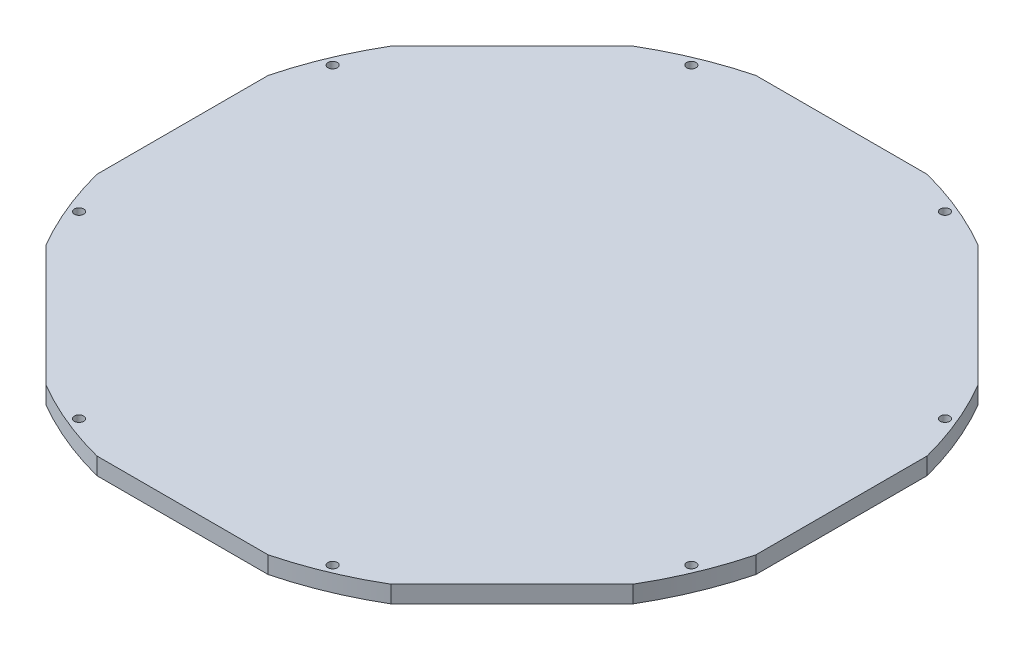
SolidWorks part; units mm, degrees
ref_plane "Front Plane" through (0, 0, 0) normal (0, 0, 1) x (1, 0, 0)
ref_plane "Top Plane" through (0, 0, 0) normal (0, 1, 0) x (1, 0, 0)
ref_plane "Right Plane" through (0, 0, 0) normal (1, 0, 0) x (0, 0, -1)
sketch "Sketch1" plane through (0, 0, 0) normal (0, 1, 0) x (1, 0, 0)
  line L1 (-50.6583, 122.3) -> (-122.3, 50.6583)
  line L2 (-122.3, 50.6583) -> (-122.3, -50.6583)
  line L3 (-122.3, -50.6583) -> (-50.6583, -122.3)
  line L4 (-50.6583, -122.3) -> (50.6583, -122.3)
  line L5 (50.6583, -122.3) -> (122.3, -50.6583)
  line L6 (122.3, -50.6583) -> (122.3, 50.6583)
  line L7 (122.3, 50.6583) -> (50.6583, 122.3)
  line L8 (50.6583, 122.3) -> (-50.6583, 122.3)
  circle A0 centre (0, 0) radius 122.3 construction
  circle A1 centre (0, 0) radius 126.365
  dimension "D2" = 252.73
  dimension "D1" = 244.6
extrude "Boss-Extrude1" add sketch "Sketch1" along normal blind 6.35 contours L4 A1 L5 L6 L7 L8 L1 L2 L3 region at (0, 0, 0)
sketch "Sketch2" plane through (0, 0, 0) normal (0, -1, 0) x (1, 0, 0)
  circle A0 centre (0, 0) radius 115.2525
  circle A1 centre (0, 0) radius 119.0625
  dimension "D1" = 238.125
  dimension "D2" = 230.505
extrude "Cut-Extrude1" cut sketch "Sketch2" against normal blind 2.667
sketch "Sketch3" plane through (0, 6.35, 0) normal (0, 1, 0) x (1, 0, 0)
  line L0 (-63.9978, 108.9605) -> (-31.7934, 122.3) construction
  line L2 (-43.181, 104.2481) -> (-51.6782, 124.7623) construction
  circle A0 centre (0, 0) radius 122.9995
  point P7 (-47.8956, 115.6303)
  point P10 (-47.0699, 113.6367)
  dimension "D1" = 245.999
hole_wizard "#8-32 Tapped Hole1" positions "Sketch4" profile "Sketch5" tap size "#8-32" standard "ANSI Inch" end condition through all
sketch "Sketch4" plane through (0, 6.35, 0) normal (0, 1, 0) x (1, 0, 0)
  point P0 (-47.0699, 113.6367)
sketch "Sketch5" plane through (-47.0699, 6.35, -113.6367) normal (1, 0, 0) x (0, 0, 1)
  line L0 (0, 0) -> (0, 6.35)
  line L1 (0, 6.35) -> (1.7272, 6.35)
  line L2 (1.7272, 6.35) -> (1.7272, 0)
  line L5 (1.7272, 0) -> (0, 0)
  line L11 (0, -6.35) -> (0, 107.95) construction
  dimension "Thru Tap Drill Dia." = 3.4544
  dimension "Thru Tap Drill Depth" = 6.35
cosmetic thread "Hole Thread1" parameters "D2"=4.1656
pattern_circular "CirPattern1" count 8 over 360 about axis through (0, 6.35, 0) along (0, -1, 0) of "#8-32 Tapped Hole1" reverse direction yes
cosmetic thread "Hole Thread2" parameters "D2"=4.1656
cosmetic thread "Hole Thread3" parameters "D2"=4.1656
cosmetic thread "Hole Thread4" parameters "D2"=4.1656
cosmetic thread "Hole Thread5" parameters "D2"=4.1656
cosmetic thread "Hole Thread6" parameters "D2"=4.1656
cosmetic thread "Hole Thread7" parameters "D2"=4.1656
cosmetic thread "Hole Thread8" parameters "D2"=4.1656
